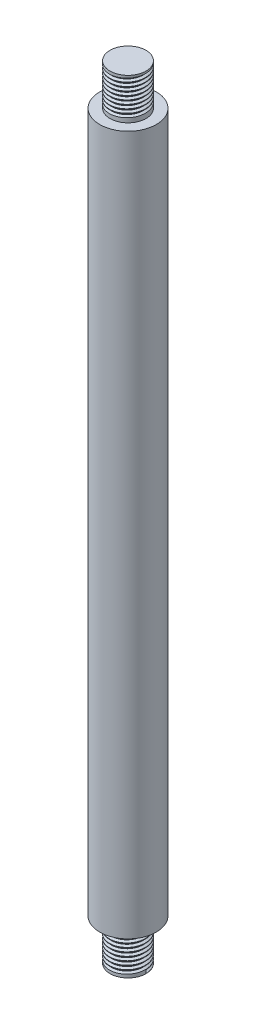
SolidWorks part; units mm, degrees
material "AISI 4340 Steel, annealed"
ref_plane "Front Plane" through (0, 0, 0) normal (0, 0, 1) x (1, 0, 0)
ref_plane "Top Plane" through (0, 0, 0) normal (0, 1, 0) x (1, 0, 0)
ref_plane "Right Plane" through (0, 0, 0) normal (1, 0, 0) x (0, 0, -1)
sketch "Sketch1" plane through (0, 0, 0) normal (0, 1, 0) x (1, 0, 0)
  circle A0 centre (0, 0) radius 11
  dimension "D1" = 22
extrude "Boss-Extrude1" add sketch "Sketch1" along normal blind 272
sketch "Sketch2" plane through (0, 272, 0) normal (0, 1, 0) x (1, 0, 0)
  circle A0 centre (0, 0) radius 17
  dimension "D1" = 34
extrude "Boss-Extrude2" add sketch "Sketch2" along normal blind 40
sketch "Sketch3" plane through (0, 0, 0) normal (0, -1, 0) x (1, 0, 0)
  circle A0 centre (0, 0) radius 17 construction
  circle A1 centre (0, 0) radius 17
extrude "Boss-Extrude3" add sketch "Sketch3" along normal blind 40
fillet "Fillet1" radius 5 1 edges at (0, -40, -17)
fillet "Fillet2" radius 5 1 edges at (0, 312, 17)
sketch "Sketch4" plane through (0, 0, 0) normal (0, 0, 1) x (1, 0, 0)
  line L1 (17, 272) -> (14.5, 272)
  line L2 (17, 272) -> (17, 285)
  line L3 (17, 285) -> (14.5, 285)
  line L4 (14.5, 272) -> (14.5, 285)
  line L5 (-17, 272) -> (-14.5, 272)
  line L6 (-17, 272) -> (-17, 293)
  line L7 (-17, 293) -> (-14.5, 293)
  line L8 (-14.5, 272) -> (-14.5, 293)
  line L10 (17, 0) -> (14.5, 0)
  line L11 (17, 0) -> (17, -13)
  line L12 (14.5, 0) -> (14.5, -13)
  line L13 (17, -13) -> (14.5, -13)
  line L14 (-17, 0) -> (-14.5, 0)
  line L15 (-17, -13) -> (-14.5, -13)
  line L16 (-17, 0) -> (-17, -13)
  line L17 (-14.5, 0) -> (-14.5, -13)
  dimension "D1" = 13
  dimension "D2" = 29
extrude "Cut-Extrude1" cut sketch "Sketch4" against normal blind 40 and the other way blind 40
sketch "Sketch5" plane through (0, -40, 0) normal (0, -1, 0) x (1, 0, 0)
  circle A0 centre (0, 0) radius 10
  dimension "D1" = 20
extrude "Cut-Extrude2" cut sketch "Sketch5" against normal blind 35
sketch "Sketch6" plane through (0, 312, 0) normal (0, 1, 0) x (1, 0, 0)
  circle A0 centre (0, 0) radius 10
  dimension "D1" = 20
extrude "Cut-Extrude3" cut sketch "Sketch6" against normal blind 35
sketch "Sketch7" plane through (0, 0, 0) normal (0, 0, 1) x (1, 0, 0)
  line L0 (0, 314.8974) -> (0, 289.8974)
  line L1 (0, -9.7955) -> (0, -34.7955)
  arc A0 (0, 289.8974) -> (0, 314.8974) centre (0, 302.3974) ccw
  arc A1 (0, -34.7955) -> (0, -9.7955) centre (0, -22.2955) ccw
  dimension "D1" = 25
  dimension "D2" = 25
revolve "Cut-Revolve4" cut sketch "Sketch7" angle 360 about axis through (0, 277, 0) along (0, 1, 0)
sketch "Sketch8" plane through (0, 0, 0) normal (0, 0, 1) x (1, 0, 0)
  line L1 (-14.5, 272) -> (14.5, 272)
  line L2 (-14.5, 272) -> (-14.5, 0)
  line L3 (-14.5, 0) -> (14.5, 0)
  line L4 (14.5, 272) -> (14.5, 0)
extrude "Cut-Extrude4" cut sketch "Sketch8" against normal mid plane 50 flip side to cut
sketch3d "3DSketch1"
  line L0 (0, 272, 0) -> (0, 0, 0) construction
  point P0 (0, 136, 0)
sketch "Sketch9" plane through (0, 0, 0) normal (0, -1, 0) x (1, 0, 0)
  circle A0 centre (0, 0) radius 7
  dimension "D1" = 14
extrude "Boss-Extrude4" add sketch "Sketch9" along normal blind 16
thread "Thread1" pitch 1.5 method cut profile "Thread Profile1" start angle 0, offset 0, length 14, pitch 1.5, diameter 14
ref_plane "Plane1" through (7, -16, 0) normal (0, 0, 1) x (1, 0, 0)
sketch "Thread Profile1" plane through (7, -16, 0) normal (0, 0, 1) x (1, 0, 0)
  line L0 (0, 0) -> (0, 1.5) construction
  line L11 (0, 0) -> (0, 1.3125)
  line L12 (0, 1.3125) -> (-0.8119, 0.8437)
  line L13 (-0.8119, 0.8437) -> (-0.8119, 0.4687)
  line L15 (-0.8119, 0.4687) -> (0, 0)
  line L17 (-0.8119, 0.6562) -> (0, 0.6562) construction
  point P2 (0, 0)
  dimension "Pitch" = 1.5
  dimension "Profile_Angle" = 60
  dimension "Profile_Land" = 0.375
  dimension "Profile_Height" = 0.8119
sketch "Sketch15" plane through (0, 272, 0) normal (0, 1, 0) x (1, 0, 0)
  circle A0 centre (0, 0) radius 7
  dimension "D1" = 14
extrude "Boss-Extrude5" add sketch "Sketch15" along normal blind 16
thread "Thread2" pitch 1.5 method cut profile "Thread Profile2" start angle 0, offset 0, length 14, pitch 1.5, diameter 14
ref_plane "Plane2" through (-7, 288, 0) normal (0, 0, 1) x (-1, 0, 0)
sketch "Thread Profile2" plane through (-7, 288, 0) normal (0, 0, 1) x (-1, 0, 0)
  line L0 (0, 0) -> (0, 1.5) construction
  line L11 (0, 0) -> (0, 1.3125)
  line L12 (0, 1.3125) -> (-0.8119, 0.8437)
  line L13 (-0.8119, 0.8437) -> (-0.8119, 0.4687)
  line L15 (-0.8119, 0.4687) -> (0, 0)
  line L17 (-0.8119, 0.6562) -> (0, 0.6562) construction
  point P2 (0, 0)
  dimension "Pitch" = 1.5
  dimension "Profile_Angle" = 60
  dimension "Profile_Land" = 0.375
  dimension "Profile_Height" = 0.8119
